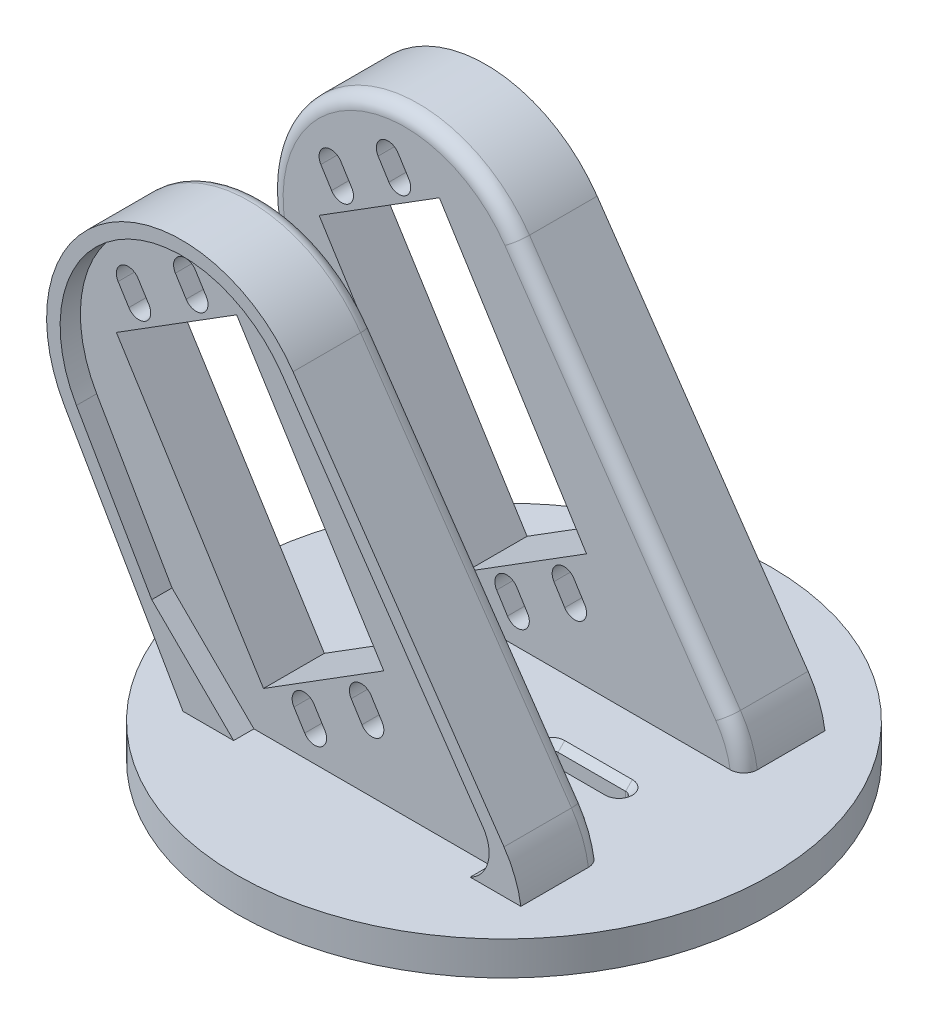
SolidWorks part; units mm, degrees
material "PLA - 20% infill"
ref_plane "Front Plane" through (0, 0, 0) normal (0, 0, 1) x (1, 0, 0)
ref_plane "Top Plane" through (0, 0, 0) normal (0, 1, 0) x (1, 0, 0)
ref_plane "Right Plane" through (0, 0, 0) normal (1, 0, 0) x (0, 0, -1)
sketch "Sketch2" plane through (0, 0, 0) normal (0, 1, 0) x (1, 0, 0)
  circle A0 centre (0, 0) radius 39.5
  dimension "D1" = 79
extrude "Boss-Extrude1" add sketch "Sketch2" along normal blind 5
sketch "Sketch3" plane through (0, 5, 0) normal (0, 1, 0) x (1, 0, 0)
  line L0 (7, 1) -> (17, 1)
  line L1 (7, -1) -> (17, -1)
  line L2 (0, -2.75) -> (0, 2.75) construction
  line L3 (-7, 1) -> (-17, 1)
  line L4 (-7, -1) -> (-17, -1)
  circle A0 centre (0, 0) radius 1.625
  arc A1 (7, 1) -> (7, -1) centre (7, 0) ccw
  arc A2 (17, -1) -> (17, 1) centre (17, 0) ccw
  arc A3 (-17, -1) -> (-17, 1) centre (-17, 0) cw
  arc A4 (-7, 1) -> (-7, -1) centre (-7, 0) cw
  dimension "D1" = 3.25
  dimension "D2" = 1
  dimension "D3" = 7
  dimension "10" = 10
extrude "Cut-Extrude1" cut sketch "Sketch3" against normal up to surface (5 mm away) and the other way through all up to face at (0, 0, 39.5)
sketch "Sketch4" plane through (0, 0, 0) normal (0, -1, 0) x (1, 0, 0)
  line L0 (-32.1201, 0) -> (32.1201, 0) construction
  line L2 (-20, -5) -> (-20, 5)
  line L4 (20, -5) -> (20, 5)
  line L5 (-20, -5) -> (20, 5) construction
  line L6 (-20, 5) -> (20, -5) construction
  line L19 (-20, 5) -> (-5, 5)
  line L20 (0, -20.0103) -> (0, 20.0103) construction
  line L21 (5, 5) -> (20, 5)
  line L22 (5, -5) -> (20, -5)
  line L23 (-20, -5) -> (-5, -5)
  arc A0 (-5, 5) -> (5, 5) centre (0, 1.6834) cw
  arc A1 (-5, -5) -> (5, -5) centre (0, -1.6834) ccw
  point P0 (0, 0)
  point P9 (0, 0)
  point P12 (0, 7.6834)
  point P16 (0, 0)
  dimension "D3" = 6
  dimension "D1" = 40
  dimension "D2" = 10
  dimension "D4" = 10
extrude "Cut-Extrude2" cut sketch "Sketch4" against normal offset from surface (2 mm away) 3 up to face at (-12, 5, 0)
ref_plane "Plane1" through (0, 0, 10.5) normal (0, 0, 1) x (1, 0, 0)
sketch "Sketch5" plane through (0, 0, 10.5) normal (0, 0, 1) x (1, 0, 0)
  line L0 (-25, 5.0002) -> (25, 5.0002)
  line L1 (22.5027, 11.3787) -> (-8.7128, 56.6622)
  line L2 (-42.5, 35.3111) -> (-25, 5.0002)
  arc A0 (25, 5.0002) -> (22.5027, 11.3787) centre (10.1527, 2.8654) ccw
  arc A1 (-8.7128, 56.6622) -> (-42.5, 35.3111) centre (-25.1795, 45.3111) ccw
  point P2 (0, 5.0002)
  dimension "D2" = 20
  dimension "D3" = 15
  dimension "D1" = 5.0002
  dimension "D4" = 55
  dimension "D5" = 35
  dimension "D6" = 50
  dimension "D7" = 120
extrude "Boss-Extrude2" add sketch "Sketch5" along normal blind 12 separate body
sketch "Sketch6" plane through (0, 0, 22.5) normal (0, 0, 1) x (1, 0, 0)
  line L1 (-17.5, 5.0002) -> (17.5, 5.0002)
  line L2 (-25, 5.0002) -> (25, 5.0002) construction
  line L4 (-29.6188, 17.0002) -> (-17.5, 5.0002)
  line L6 (-40.7679, 36.3111) -> (-23.2679, 6.0002)
  line L7 (20.8561, 10.2436) -> (-10.3594, 55.5271)
  line L12 (-40.7679, 36.3111) -> (-29.6188, 17.0002)
  line L13 (19.4186, 12.3289) -> (-10.3594, 55.5271)
  arc A4 (-10.3594, 55.5271) -> (-40.7679, 36.3111) centre (-25.1795, 45.3111) ccw
  arc A5 (-10.3594, 55.5271) -> (-40.7679, 36.3111) centre (-25.1795, 45.3111) ccw
  arc A7 (19.4186, 12.3289) -> (17.5, 5.0002) centre (15.3019, 9.4911) cw
  point P6 (0, 5.0002)
  dimension "D2" = 2
  dimension "D3" = 5
  dimension "D1" = 35
  dimension "D4" = 12
extrude "Cut-Extrude4" cut sketch "Sketch6" against normal blind 3
sketch "Sketch8" plane through (0, 0, 19.5) normal (0, 0, 1) x (1, 0, 0)
  line L0 (-34.7952, 60.5275) -> (0, 5.0002) construction
  line L1 (-37.8517, 45.6309) -> (-16.081, 10.8885)
  line L2 (-16.081, 10.8885) -> (1.7139, 22.0394)
  line L3 (1.7139, 22.0394) -> (-20.0568, 56.7818)
  line L4 (-29.1207, 57.5927) -> (-27.5277, 55.0505)
  line L5 (-26.1549, 59.4511) -> (-24.5619, 56.909)
  line L6 (-3.1021, 16.0712) -> (-1.5091, 13.5291)
  line L7 (-0.1363, 17.9297) -> (1.4567, 15.3876)
  line L8 (17.5, 5.0002) -> (-17.5, 5.0002) construction
  line L9 (-20.0568, 56.7818) -> (-37.8517, 45.6309)
  line L10 (-36.034, 71.9208) -> (5.9007, 5) construction
  line L11 (-9.1714, 39.4106) -> (-26.9663, 28.2597) construction
  line L12 (39.5, 5) -> (-39.5, 5) construction
  line L13 (-11.5758, 10.7613) -> (-9.9829, 8.2192)
  line L14 (-8.61, 12.6198) -> (-7.017, 10.0776)
  line L15 (-34.6287, 54.1412) -> (-33.0357, 51.5991)
  line L16 (-37.5945, 52.2827) -> (-36.0015, 49.7406)
  arc A0 (-10.3594, 55.5271) -> (-40.7679, 36.3111) centre (-25.1795, 45.3111) ccw construction
  arc A1 (-26.1549, 59.4511) -> (-29.1207, 57.5927) centre (-27.6378, 58.5219) ccw
  arc A2 (-27.5277, 55.0505) -> (-24.5619, 56.909) centre (-26.0448, 55.9798) ccw
  arc A3 (-0.1363, 17.9297) -> (-3.1021, 16.0712) centre (-1.6192, 17.0005) ccw
  arc A4 (-1.5091, 13.5291) -> (1.4567, 15.3876) centre (-0.0262, 14.4583) ccw
  arc A5 (-11.5758, 10.7613) -> (-8.61, 12.6198) centre (-10.0929, 11.6905) cw
  arc A6 (-7.017, 10.0776) -> (-9.9829, 8.2192) centre (-8.5, 9.1484) cw
  arc A7 (-37.5945, 52.2827) -> (-34.6287, 54.1412) centre (-36.1116, 53.212) cw
  arc A8 (-33.0357, 51.5991) -> (-36.0015, 49.7406) centre (-34.5186, 50.6698) cw
  point P23 (-28.9542, 51.2064)
  dimension "D2" = 3
  dimension "D3" = 1.75
  dimension "D6" = 1.75
  dimension "D7" = 23
  dimension "D9" = 23
  dimension "D4" = 5
  dimension "D1" = 21
  dimension "D5" = 3
  dimension "D8" = 41
  dimension "D10" = 11
extrude "Cut-Extrude5" cut sketch "Sketch8" against normal up to surface (9 mm away) up to face at (-7.7197, 25.9457, 10.5)
sketch "Sketch9" plane through (0, 5, 0) normal (0, 1, 0) x (1, 0, 0)
  circle A1 centre (0, 0) radius 3
  dimension "D1" = 6
extrude "Cut-Extrude6" cut sketch "Sketch9" against normal offset from surface (2 mm away) 1 up to face at (12, 2, 0)
fillet "Fillet3" radius 2 4 edges at (24.1203, 8.3339, 10.5) (-33.75, 20.1557, 10.5) (-35.8636, 62.2182, 10.5) (6.895, 34.0205, 10.5)
chamfer "Chamfer6" distance 1 angle 45 8 edges at (12, 5, 1) (18, 5, 0) (6, 5, 0) (12, 5, -1) (-12, 5, 1) (-6, 5, 0) (-18, 5, 0) (-12, 5, -1)
mirror "Mirror1" about plane through (0, 0, 0) normal (0, 0, 1) of bodies 107
